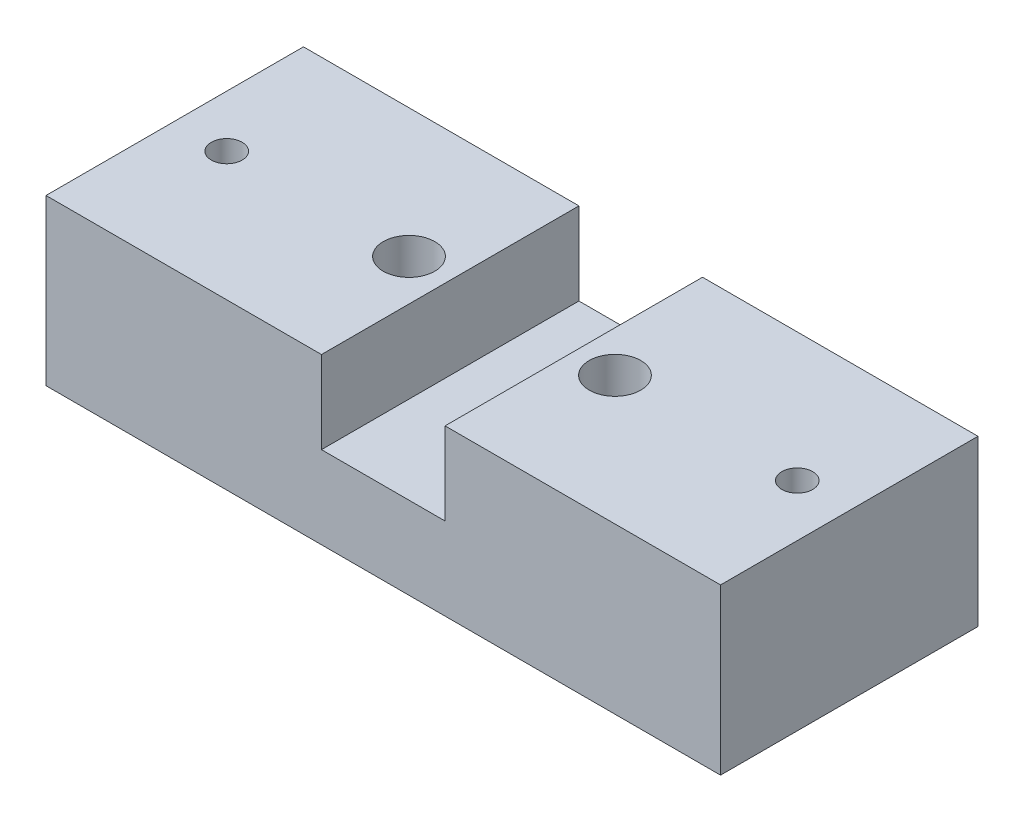
SolidWorks part; units mm, degrees
ref_plane "Płaszczyzna przednia" through (0, 0, 0) normal (0, 0, 1) x (1, 0, 0)
ref_plane "Płaszczyzna górna" through (0, 0, 0) normal (0, 1, 0) x (1, 0, 0)
ref_plane "Płaszczyzna prawa" through (0, 0, 0) normal (1, 0, 0) x (0, 0, -1)
sketch "Sketch1" plane through (0, 0, 0) normal (0, 0, 1) x (1, 0, 0)
  line L0 (26.75, 16) -> (26.75, 8)
  line L1 (0, 0) -> (65.5, 0)
  line L2 (0, 0) -> (0, 16)
  line L3 (0, 16) -> (26.75, 16)
  line L4 (65.5, 0) -> (65.5, 16)
  line L5 (26.75, 8) -> (38.75, 8)
  line L6 (38.75, 8) -> (38.75, 16)
  line L7 (38.75, 16) -> (65.5, 16)
  dimension "D1" = 65.5
  dimension "D2" = 16
  dimension "D3" = 26.75
  dimension "D4" = 26.75
  dimension "D5" = 8
extrude "Boss-Extrude1" add sketch "Sketch1" along normal blind 25
hole_wizard "Ø3.0mm Dowel Hole1" positions "Sketch2" profile "Sketch4" hole size "Ø3.0" standard "ANSI Metric" end condition through all
sketch "Sketch2" plane through (0, 16, 0) normal (0, 1, 0) x (1, 0, 0)
  line L2 (65.5, -25) -> (38.75, -25) construction
  line L3 (65.5, -25) -> (65.5, 0) construction
  line L4 (0, -25) -> (0, 0) construction
  point P0 (5.05, -12.5)
  point P2 (60.45, -12.5)
  point P27 (0, 0)
  point P28 (0, 0)
  dimension "D1" = 5.05
  dimension "D2" = 5.05
  dimension "D3" = 12.5
sketch "Sketch4" plane through (5.05, 16, 12.5) normal (1, 0, 0) x (0, 0, 1)
  line L0 (0, 0) -> (0, 16)
  line L1 (0, 16) -> (1.5, 16)
  line L2 (1.5, 16) -> (1.5, 0)
  line L5 (1.5, 0) -> (0, 0)
  line L11 (0, -6.35) -> (0, 107.95) construction
  dimension "Thru Hole Dia." = 3
  dimension "Thru Hole Depth" = 16
sketch "Sketch5" plane through (0, 0, 0) normal (0, 1, 0) x (1, 0, 0)
  line L0 (65.5, -25) -> (38.75, -25) construction
  line L1 (0, -25) -> (0, 0) construction
  circle A0 centre (50.65, -13) radius 5
  circle A1 centre (14.45, -13) radius 5
  dimension "D1" = 10
  dimension "D2" = 10
  dimension "D4" = 36.2
  dimension "D5" = 14.45
  dimension "D3" = 12
extrude "Cut-Extrude1" cut sketch "Sketch5" along normal blind 4
hole_wizard "Ø5.0mm Dowel Hole1" positions "Sketch6" profile "Sketch7" hole size "Ø5.0" standard "ANSI Metric" end condition through all
sketch "Sketch6" plane through (0, 16, 0) normal (0, 1, 0) x (1, 0, 0)
  line L0 (65.5, -25) -> (38.75, -25) construction
  line L1 (0, -25) -> (0, 0) construction
  point P0 (42.75, -12.5)
  point P2 (22.75, -12.5)
  dimension "D1" = 12.5
  dimension "D2" = 20
  dimension "D3" = 22.75
sketch "Sketch7" plane through (42.75, 16, 12.5) normal (1, 0, 0) x (0, 0, 1)
  line L0 (0, 0) -> (0, 16)
  line L1 (0, 16) -> (2.5, 16)
  line L2 (2.5, 16) -> (2.5, 0)
  line L5 (2.5, 0) -> (0, 0)
  line L11 (0, -6.35) -> (0, 107.95) construction
  dimension "Thru Hole Dia." = 5
  dimension "Thru Hole Depth" = 16
